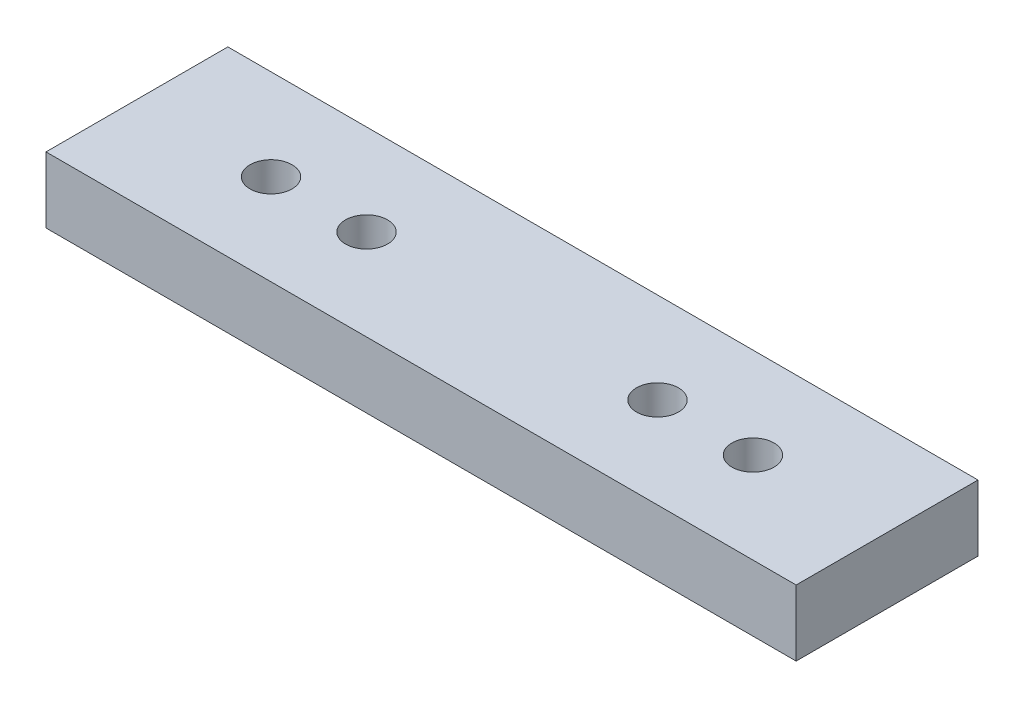
SolidWorks part; units mm, degrees
ref_plane "Front Plane" through (0, 0, 0) normal (0, 0, 1) x (1, 0, 0)
ref_plane "Top Plane" through (0, 0, 0) normal (0, 1, 0) x (1, 0, 0)
ref_plane "Right Plane" through (0, 0, 0) normal (1, 0, 0) x (0, 0, -1)
sketch "Sketch1" plane through (0, 0, 0) normal (0, 1, 0) x (1, 0, 0)
  line L1 (-20.955, 5.08) -> (20.955, 5.08)
  line L2 (-20.955, 5.08) -> (-20.955, -5.08)
  line L3 (-20.955, -5.08) -> (20.955, -5.08)
  line L4 (20.955, 5.08) -> (20.955, -5.08)
  line L5 (-20.955, 5.08) -> (20.955, -5.08) construction
  line L6 (-20.955, -5.08) -> (20.955, 5.08) construction
  point P0 (0, 0)
  dimension "D1" = 41.91
  dimension "D2" = 10.16
extrude "Boss-Extrude1" add sketch "Sketch1" along normal blind 3.683
sketch "Sketch2" plane through (0, 0, 0) normal (0, -1, 0) x (1, 0, 0)
  line L0 (0, 5.08) -> (0, -5.08) construction
  line L1 (-20.955, 5.08) -> (20.955, 5.08) construction
  line L2 (20.955, -5.08) -> (-20.955, -5.08) construction
  line L3 (-10.795, 5.08) -> (-10.795, -5.08) construction
  line L4 (-20.955, -5.08) -> (-20.955, 5.08) construction
  circle A0 centre (-13.462, 0) radius 1.174
  circle A1 centre (-8.128, 0) radius 1.174
  circle A2 centre (8.128, 0) radius 1.174
  circle A3 centre (13.462, 0) radius 1.174
  point P10 (-10.795, 0)
  dimension "D3" = 7.493
  dimension "D1" = 10.16
  dimension "D2" = 10.795
extrude "Boss-Extrude2" [suppressed] add sketch "Sketch2" along normal blind 0.635
extrude "Cut-Extrude1" cut sketch "Sketch2<2>" against normal through all
sketch "Sketch2<2>" plane through (0, 0, 0) normal (0, -1, 0) x (1, 0, 0) same geometry as "Sketch2"
